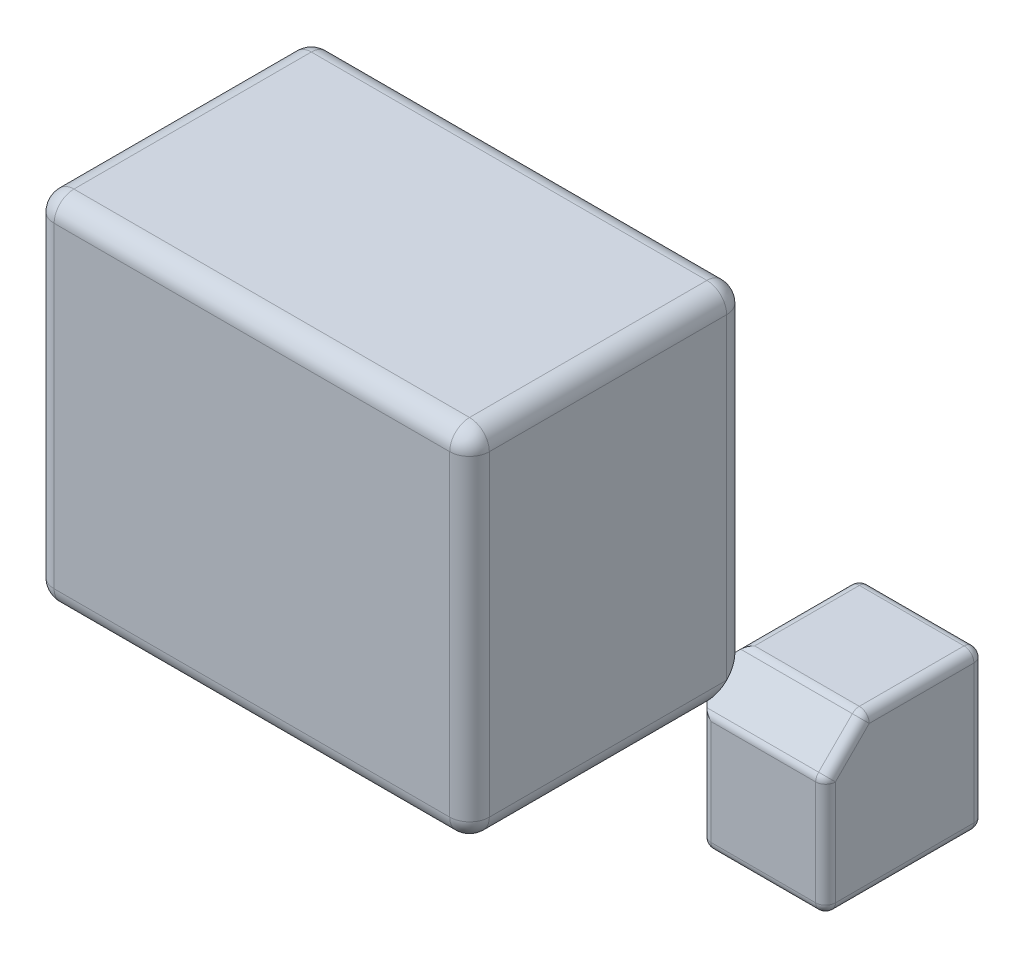
SolidWorks part; units mm, degrees
ref_plane "Front Plane" through (0, 0, 0) normal (0, 0, 1) x (1, 0, 0)
ref_plane "Top Plane" through (0, 0, 0) normal (0, 1, 0) x (1, 0, 0)
ref_plane "Right Plane" through (0, 0, 0) normal (1, 0, 0) x (0, 0, -1)
sketch "Sketch1" plane through (0, 0, 0) normal (0, 0, 1) x (1, 0, 0)
  line L1 (0, 0) -> (22, 0)
  line L2 (0, 0) -> (0, 18)
  line L3 (0, 18) -> (22, 18)
  line L4 (22, 0) -> (22, 18)
  dimension "D1" = 22
  dimension "D2" = 18
extrude "Boss-Extrude1" add sketch "Sketch1" along normal blind 14
sketch "Sketch2" plane through (0, 0, 0) normal (0, 0, -1) x (-1, 0, 0)
  line L0 (-22, 0) -> (-22, 18) construction
  line L1 (-20, 2) -> (-28, 2)
  line L2 (-20, 2) -> (-20, -6)
  line L3 (-20, -6) -> (-28, -6)
  line L4 (-28, 2) -> (-28, -6)
  line L5 (0, 0) -> (-22, 0) construction
  dimension "D1" = 2
  dimension "D2" = 2
  dimension "D3" = 8
  dimension "D4" = 8
shell "Shell1" thickness 1
extrude "Boss-Extrude3" add sketch "Sketch2" along normal blind 6 and the other way blind 2 contours L3 L4 L1 L2
chamfer "Chamfer2" distance 2 angle 45 3 edges at (25, 2, 2) (20, 2, -3) (20, -3, 2)
fillet "Fillet1" radius 1 12 edges at (0, 9, 0) (10, 0, 0) (22, 10, 0) (11, 18, 0) (11, 0, 14) (22, 9, 14) (11, 18, 14) (0, 18, 7) (22, 18, 7) (22, 0, 8) (0, 0, 7) (0, 9, 14)
fillet "Fillet2" radius 0.5 18 edges at (28, -6, -2) (24, -6, -6) (21, -6, 1) (25, -6, 2) (20, -6, -3) (20, -3, -6) (20, 0, -3) (20, -3, 0) (25, 0, 2) (21, 1, -6) (25, 2, -6) (28, 2, -3) (25, 2, 0) (22, 2, -3) (28, -3, 2) (28, -2, -6) (22, -3, 2) (28, 1, 1)
